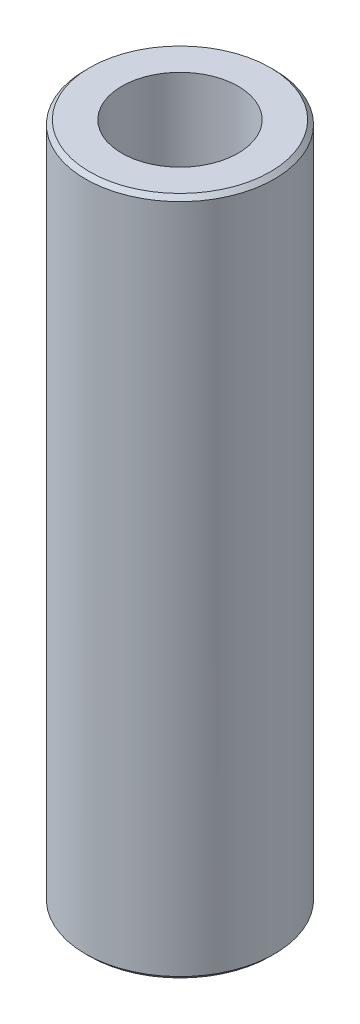
SolidWorks part; units mm, degrees
ref_plane "Front Plane" through (0, 0, 0) normal (0, 0, 1) x (1, 0, 0)
ref_plane "Top Plane" through (0, 0, 0) normal (0, 1, 0) x (1, 0, 0)
ref_plane "Right Plane" through (0, 0, 0) normal (1, 0, 0) x (0, 0, -1)
sketch "Sketch1" plane through (0, 0, 0) normal (0, 1, 0) x (1, 0, 0)
  circle A0 centre (0, 0) radius 15
  dimension "SHAFT_OD" = 30
extrude "Boss-Extrude1" add sketch "Sketch1" along normal blind 107.8816
sketch "Sketch2" plane through (0, 0, 0) normal (0, 1, 0) x (1, 0, 0)
  circle A0 centre (0, 0) radius 9.2299
  dimension "BORE_D" = 18.4598
extrude "Cut-Extrude1" cut sketch "Sketch2" along normal through all
chamfer "Chamfer1" distance 0.6613 angle 45 2 edges at (0, 107.8816, 15) (0, 0, 15)
